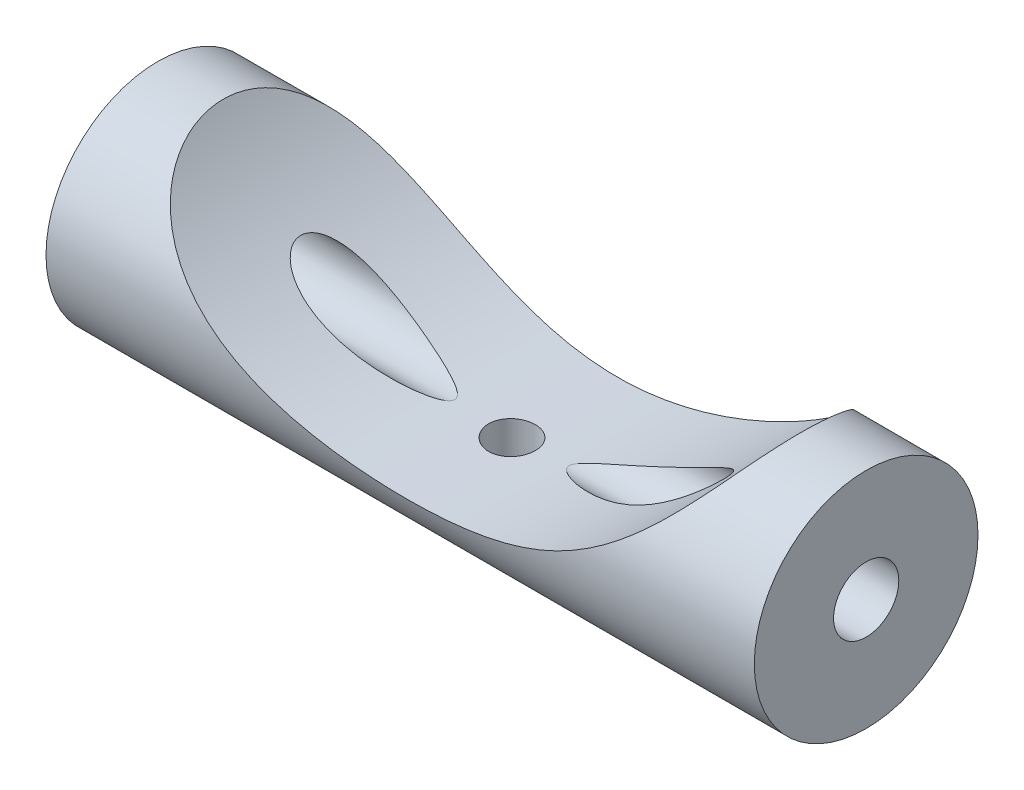
SolidWorks part; units mm, degrees
ref_plane "Front Plane" through (0, 0, 0) normal (0, 0, 1) x (1, 0, 0)
ref_plane "Top Plane" through (0, 0, 0) normal (0, 1, 0) x (1, 0, 0)
ref_plane "Right Plane" through (0, 0, 0) normal (1, 0, 0) x (0, 0, -1)
sketch "Sketch1" plane through (0, 0, 0) normal (1, 0, 0) x (0, 0, -1)
  circle A0 centre (0, 0) radius 6
  dimension "D1" = 12
extrude "Boss-Extrude1" add sketch "Sketch1" along normal mid plane 38
sketch "Sketch2" plane through (0, 0, 0) normal (0, 0, 1) x (1, 0, 0)
  line L0 (19, 6) -> (-19, 6) construction
  line L1 (0, -2) -> (0, 17) construction
  line L3 (-19, -6) -> (19, -6) construction
  arc A0 (-15.4919, 6) -> (15.4919, 6) centre (0, 17) ccw
  dimension "D1" = 19
  dimension "D2" = 4
extrude "Cut-Extrude1" cut sketch "Sketch2" against normal through all and the other way through all
sketch "Sketch3" plane through (0, 0, 0) normal (1, 0, 0) x (0, 0, -1)
  circle A0 centre (0, 0) radius 1.75
  dimension "D1" = 3.5
extrude "Cut-Extrude2" cut sketch "Sketch3" against normal mid plane 40
sketch "Sketch4" plane through (0, 0, 0) normal (0, 1, 0) x (1, 0, 0)
  circle A0 centre (0, 0) radius 1.25
  dimension "D1" = 2.5
extrude "Cut-Extrude3" cut sketch "Sketch4" against normal through all
